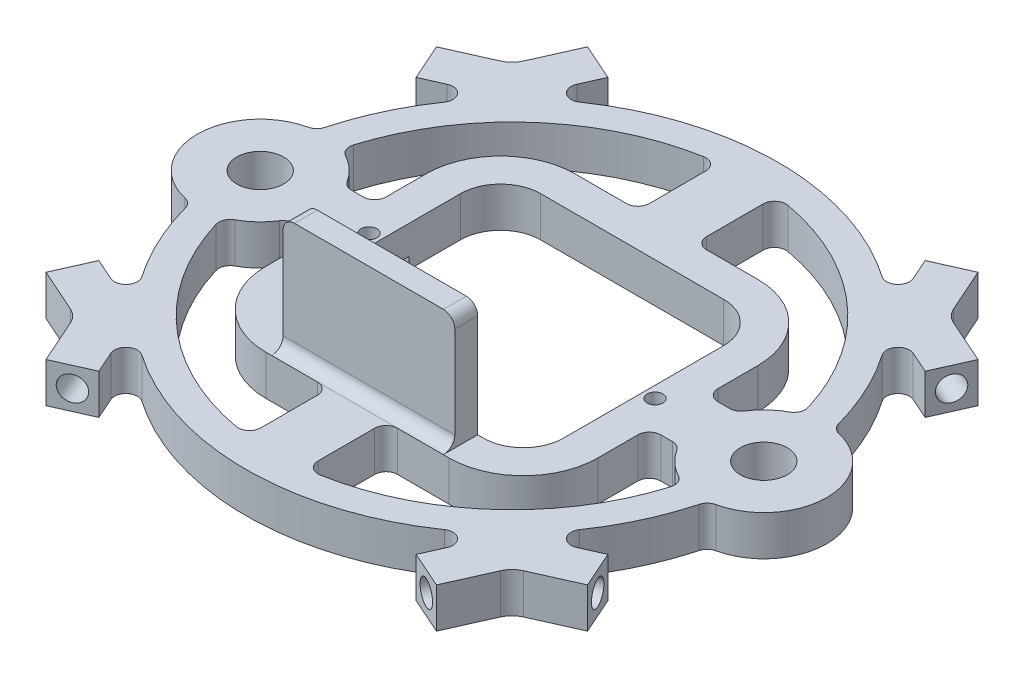
SolidWorks part; units mm, degrees
ref_plane "Front Plane" through (0, 0, 0) normal (0, 0, 1) x (1, 0, 0)
ref_plane "Top Plane" through (0, 0, 0) normal (0, 1, 0) x (1, 0, 0)
ref_plane "Right Plane" through (0, 0, 0) normal (1, 0, 0) x (0, 0, -1)
sketch "Sketch1" plane through (0, 0, 0) normal (0, 1, 0) x (1, 0, 0)
  line L0 (-20.32, 34.29) -> (20.32, 34.29)
  line L1 (-20.32, 26.67) -> (20.32, 26.67)
  line L2 (-29.21, 17.78) -> (-29.21, -17.78)
  line L3 (-20.32, -26.67) -> (20.32, -26.67)
  line L4 (29.21, 17.78) -> (29.21, -17.78)
  line L5 (-29.21, 26.67) -> (29.21, -26.67) construction
  line L6 (-29.21, -26.67) -> (29.21, 26.67) construction
  line L7 (36.83, 17.78) -> (36.83, -17.78)
  line L8 (-20.32, -34.29) -> (20.32, -34.29)
  line L9 (-36.83, 17.78) -> (-36.83, -17.78)
  arc A0 (-29.21, -17.78) -> (-20.32, -26.67) centre (-20.32, -17.78) ccw
  arc A1 (20.32, -26.67) -> (29.21, -17.78) centre (20.32, -17.78) ccw
  arc A2 (20.32, 26.67) -> (29.21, 17.78) centre (20.32, 17.78) cw
  arc A3 (-20.32, 26.67) -> (-29.21, 17.78) centre (-20.32, 17.78) ccw
  arc A4 (20.32, 34.29) -> (36.83, 17.78) centre (20.32, 17.78) cw
  arc A5 (20.32, -34.29) -> (36.83, -17.78) centre (20.32, -17.78) ccw
  arc A6 (-36.83, -17.78) -> (-20.32, -34.29) centre (-20.32, -17.78) ccw
  arc A7 (-20.32, 34.29) -> (-36.83, 17.78) centre (-20.32, 17.78) ccw
  point P0 (0, 0)
  dimension "D3" = 8.89
  dimension "D1" = 58.42
  dimension "D2" = 53.34
  dimension "D4" = 7.62
extrude "Boss-Extrude1" add sketch "Sketch1" along normal mid plane 8.89
sketch "Sketch2" plane through (0, 0, 0) normal (0, 1, 0) x (1, 0, 0)
  line L0 (-43.4366, 6.35) -> (-36.83, 6.35)
  line L1 (-36.83, 17.78) -> (-36.83, -17.78) construction
  line L2 (-36.83, 6.35) -> (-36.83, -6.35)
  line L3 (-36.83, -6.35) -> (-43.4366, -6.35)
  circle A0 centre (-55.88, 0) radius 5.207
  arc A2 (-43.4366, 6.35) -> (-43.4366, -6.35) centre (-55.88, 0) ccw
  point P9 (-36.83, 0)
  point P12 (-36.83, 0)
  dimension "D1" = 10.414
  dimension "D3" = 13.97
  dimension "D2" = 55.88
  dimension "D4" = 12.7
extrude "Boss-Extrude2" add sketch "Sketch2" along normal mid plane 8.89
mirror "Mirror1" about plane through (0, 0, 0) normal (1, 0, 0) of "Boss-Extrude2"
sketch "Sketch3" plane through (0, 0, 0) normal (0, 1, 0) x (1, 0, 0)
  arc A0 (43.4366, -6.35) -> (43.4366, 6.35) centre (55.88, 0) ccw construction
  arc A1 (-43.4366, 6.35) -> (-43.4366, -6.35) centre (-55.88, 0) ccw construction
  arc A2 (51.0489, -13.1081) -> (57.3989, -13.8872) centre (55.88, 0) ccw
  arc A3 (-51.0489, 13.1081) -> (-57.3989, 13.8872) centre (-55.88, 0) ccw
  arc A4 (-57.3989, -13.8872) -> (57.3989, -13.8872) centre (0, 0) ccw
  arc A5 (-51.0489, -13.1081) -> (51.0489, -13.1081) centre (0, 0) ccw
  circle A6 centre (0, 0) radius 55.88 construction
  arc A7 (-57.3989, -13.8872) -> (-51.0489, -13.1081) centre (-55.88, 0) ccw
  arc A8 (57.3989, 13.8872) -> (51.0489, 13.1081) centre (55.88, 0) ccw
  circle A9 centre (0, 0) radius 52.705 construction
  circle A10 centre (0, 0) radius 59.055 construction
  arc A11 (57.3989, 13.8872) -> (-57.3989, 13.8872) centre (0, 0) ccw
  arc A12 (51.0489, 13.1081) -> (-51.0489, 13.1081) centre (0, 0) ccw
  point P11 (59.055, 0)
  point P17 (52.705, 0)
  dimension "D1" = 3.175
  dimension "D2" = 3.175
extrude "Boss-Extrude3" add sketch "Sketch3" along normal mid plane 8.89
sketch "Sketch5" plane through (0, 0, 0) normal (0, 1, 0) x (1, 0, 0)
  line L0 (0, 0) -> (0, 50000) construction
  line L1 (-6.35, 52.3211) -> (-6.35, 34.29)
  line L2 (20.32, 34.29) -> (-20.32, 34.29) construction
  line L3 (-6.35, 34.29) -> (6.35, 34.29)
  line L4 (6.35, 34.29) -> (6.35, 52.3211)
  line L5 (-6.35, -52.3211) -> (-6.35, -34.29)
  line L6 (-20.32, -34.29) -> (20.32, -34.29) construction
  line L7 (-6.35, -34.29) -> (6.35, -34.29)
  line L8 (6.35, -34.29) -> (6.35, -52.3211)
  arc A0 (51.0489, 13.1081) -> (-51.0489, 13.1081) centre (0, 0) ccw construction
  arc A1 (-51.0489, -13.1081) -> (51.0489, -13.1081) centre (0, 0) ccw construction
  arc A2 (6.35, 52.3211) -> (-6.35, 52.3211) centre (0, 0) ccw
  arc A3 (-6.35, -52.3211) -> (6.35, -52.3211) centre (0, 0) ccw
  point P17 (0, 34.29)
  point P20 (0, -34.29)
  dimension "D1" = 12.7
extrude "Boss-Extrude4" add sketch "Sketch5" along normal mid plane 8.89
fillet "Fillet1" radius 2.54 24 edges at (43.4366, 0, -6.35) (36.83, 0, -6.35) (43.4366, 0, 6.35) (36.83, 0, 6.35) (6.35, 0, 52.3211) (6.35, 0, 34.29) (-6.35, 0, 34.29) (-6.35, 0, 52.3211) (-51.0489, 0, -13.1081) (-43.4366, 0, -6.35) (-43.4366, 0, 6.35) (-51.0489, 0, 13.1081) (-57.3989, 0, 13.8872) (-57.3989, 0, -13.8872) (-36.83, 0, 6.35) (-36.83, 0, -6.35) (-6.35, 0, -34.29) (-6.35, 0, -52.3211) (6.35, 0, -34.29) (6.35, 0, -52.3211) (57.3989, 0, 13.8872) (57.3989, 0, -13.8872) (51.0489, 0, -13.1081) (51.0489, 0, 13.1081)
sketch "Sketch6" plane through (0, -4.445, 0) normal (0, -1, 0) x (1, 0, 0)
  line L0 (-27.94, -6.35) -> (-27.94, 6.35)
  line L2 (-27.94, 6.35) -> (-31.75, 6.35)
  line L3 (-36.83, 1.27) -> (-36.83, -1.27)
  line L4 (-31.75, -6.35) -> (-27.94, -6.35)
  line L5 (0, 0) -> (0, 50000) construction
  line L6 (27.94, 6.35) -> (31.75, 6.35)
  line L7 (36.83, 1.27) -> (36.83, -1.27)
  line L8 (31.75, -6.35) -> (27.94, -6.35)
  line L9 (27.94, -6.35) -> (27.94, 6.35)
  arc A0 (-31.75, 6.35) -> (-36.83, 1.27) centre (-31.75, 1.27) ccw
  arc A1 (-36.83, -1.27) -> (-31.75, -6.35) centre (-31.75, -1.27) ccw
  arc A2 (31.75, 6.35) -> (36.83, 1.27) centre (31.75, 1.27) cw
  arc A3 (36.83, -1.27) -> (31.75, -6.35) centre (31.75, -1.27) cw
  point P10 (-27.94, 0)
  dimension "D1" = 5.08
  dimension "D2" = 6.35
  dimension "D3" = 8.89
  dimension "D4" = 27.94
extrude "Cut-Extrude1" cut sketch "Sketch6" against normal blind 2.54
sketch "Sketch7" plane through (0, -1.905, 0) normal (0, -1, 0) x (1, 0, 0)
  line L0 (-29.21, 6.35) -> (-29.21, -6.35) construction
  line L1 (0, 0) -> (0, -50000) construction
  circle A0 centre (-31.75, 0) radius 1.7526
  circle A1 centre (31.75, 0) radius 1.7526
  dimension "D1" = 3.5052
  dimension "D2" = 2.54
extrude "Cut-Extrude2" cut sketch "Sketch7" against normal up to next
sketch "Sketch8" plane through (0, 4.445, 0) normal (0, 1, 0) x (1, 0, 0)
  line L1 (-19.05, -26.67) -> (19.05, -26.67)
  line L2 (-20.32, -26.67) -> (20.32, -26.67) construction
  point P2 (0, -26.67)
  point P5 (0, -26.67)
  dimension "D1" = 38.1
extrude "Extrude-Thin1" add sketch "Sketch8" along normal blind 25.4 thin thin type one direction wall 5.08
fillet "Fillet2" radius 2.54 3 edges at (-19.05, 29.845, 29.21) (0, 4.445, 31.75) (19.05, 29.845, 29.21)
sketch "Sketch12" plane through (0, 4.445, 0) normal (0, 1, 0) x (1, 0, 0)
  line L0 (0, 0) -> (0, -50000) construction
  line L1 (0, 0) -> (35355.3391, -35355.3391) construction
  line L2 (51.7144, -37.3254) -> (56.4777, -35.2046)
  line L3 (56.4777, -35.2046) -> (60.0936, -43.326)
  line L4 (60.0936, -43.326) -> (48.4916, -48.4916)
  line L5 (51.7144, -37.3254) -> (41.7582, -41.7582) construction
  line L6 (35.2046, -56.4777) -> (43.326, -60.0936)
  line L7 (43.326, -60.0936) -> (48.4916, -48.4916)
  line L8 (37.3254, -51.7144) -> (35.2046, -56.4777)
  line L9 (33.5615, -48.5914) -> (31.7654, -46.7953)
  line L10 (31.7654, -46.7953) -> (46.7953, -31.7654)
  line L11 (46.7953, -31.7654) -> (48.5914, -33.5615)
  arc A0 (33.5615, -48.5914) -> (37.3254, -51.7144) centre (35.005, -50.6813) cw
  arc A1 (-56.9968, -15.4551) -> (56.9968, -15.4551) centre (0, 0) ccw construction
  arc A2 (-56.9968, -15.4551) -> (56.9968, -15.4551) centre (0, 0) ccw
  arc A3 (48.5914, -33.5615) -> (51.7144, -37.3254) centre (50.6813, -35.005) ccw
  point P8 (41.7582, -41.7582)
  point P23 (44.6904, -35.6424)
  point P24 (39.2804, -39.2804)
  point P25 (44.1806, -35.2666)
  dimension "D2" = 2.54
  dimension "D1" = 45
  dimension "D3" = 69
  dimension "D4" = 8.89
  dimension "D5" = 12.7
  dimension "D6" = 2.54
extrude "Boss-Extrude6" add sketch "Sketch12" against normal up to surface (8.89 mm away) contours L8 L6 L7 L4 L3 L2 A3 L11 L10 L9 A0 up to face at (-29.7794, -4.445, 24.148)
sketch "Sketch14" plane through (-15.1615, 0, 34.0533) normal (-0.4067, 0, 0.9135) x (0.9135, 0, 0.4067)
  line L0 (64.0226, -4.445) -> (55.1326, -4.445) construction
  line L1 (64.0226, -4.445) -> (64.0226, 4.445) construction
  line L2 (55.1326, 4.445) -> (64.0226, 4.445) construction
  line L3 (55.1326, -4.445) -> (55.1326, 4.445) construction
  line L4 (64.0226, -4.445) -> (55.1326, -4.445) construction
  line L5 (64.0226, -4.445) -> (64.0226, 4.445) construction
  line L6 (55.1326, 4.445) -> (64.0226, 4.445) construction
  line L7 (55.1326, -4.445) -> (55.1326, 4.445) construction
  line L8 (59.5776, 4.445) -> (59.5776, -4.445) construction
  line L9 (55.1326, 0) -> (64.0226, 0) construction
  circle A0 centre (59.5776, 0) radius 2.7305
  dimension "D1" = 5.461
extrude "Cut-Extrude3" cut sketch "Sketch14" against normal blind 10.16
ref_plane "Plane1" through (0, 0, 0) normal (-0.7071, 0, 0.7071) x (0, 1, 0)
mirror "Mirror2" about plane through (0, 0, 0) normal (-0.7071, 0, 0.7071) of "Cut-Extrude3"
fillet "Fillet3" radius 5.08 1 edges at (48.4916, 0, 48.4916)
pattern_circular "CirPattern1" count 4 over 360 about axis through (0, 4.445, 0) along (0, 1, 0) of "Boss-Extrude6", "Cut-Extrude3", "Fillet3", "Mirror2"
equation "\"depth\"=0.35"
equation "\"D1@Boss-Extrude1\"=\"depth\""
equation "\"D1@Boss-Extrude3\"=\"depth\""
equation "\"D1@Boss-Extrude4\"=\"depth\""
